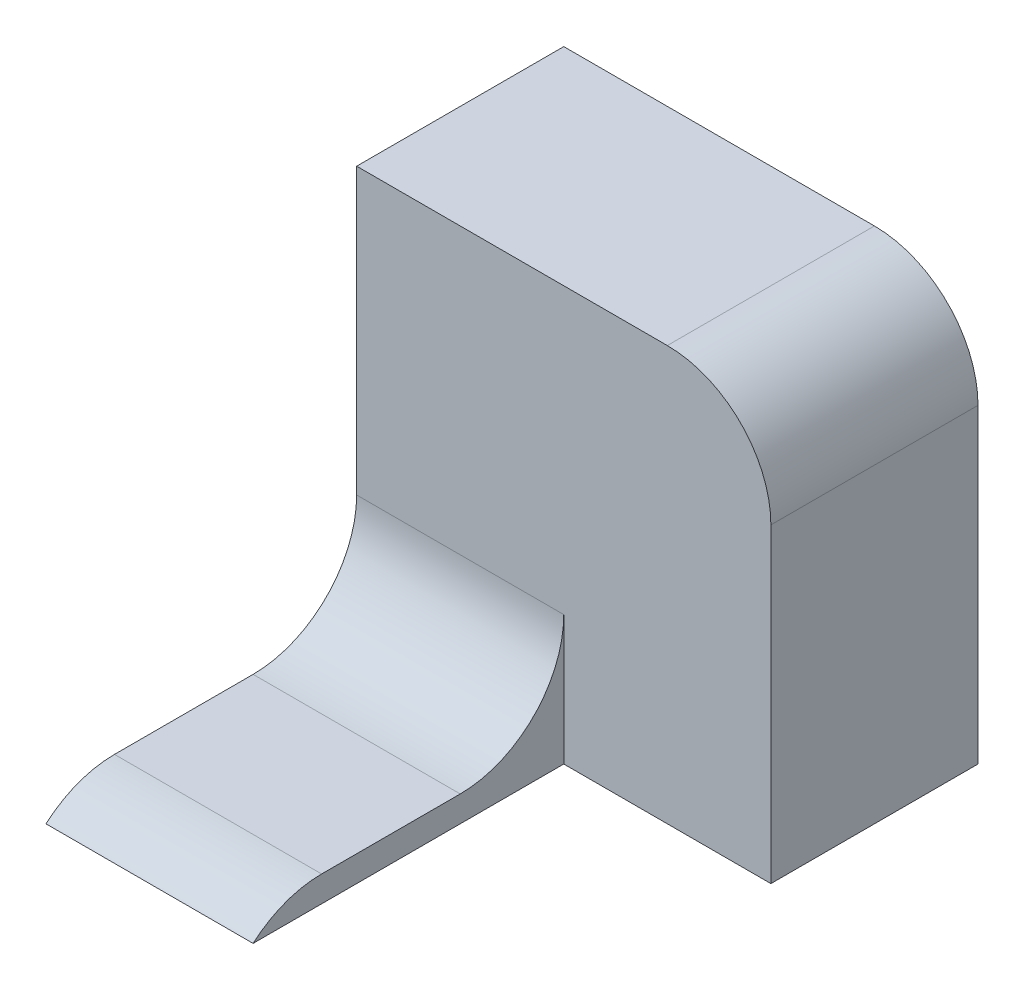
SolidWorks part; units mm, degrees
ref_plane "Front Plane" through (0, 0, 0) normal (0, 0, 1) x (1, 0, 0)
ref_plane "Top Plane" through (0, 0, 0) normal (0, 1, 0) x (1, 0, 0)
ref_plane "Right Plane" through (0, 0, 0) normal (1, 0, 0) x (0, 0, -1)
sketch "Sketch1" plane through (0, 0, 0) normal (0, 0, 1) x (1, 0, 0)
  line L1 (-30, -2.5) -> (-10, -2.5)
  line L2 (-10, -2.5) -> (-10, 0)
  line L3 (-10, 0) -> (-30, 0)
  line L4 (-30, 0) -> (-30, -2.5)
  dimension "D1" = 20
  dimension "Width" = 2.5
extrude "Boss-Extrude1" add sketch "Sketch1" along normal blind 30
sketch "Sketch2" plane through (0, 0, 0) normal (0, 0, 1) x (1, 0, 0)
  line L1 (-30, -2.5) -> (10, -2.5)
  line L2 (10, -2.5) -> (10, 37.5)
  line L3 (10, 37.5) -> (-30, 37.5)
  line L4 (-30, 37.5) -> (-30, -2.5)
  dimension "D1" = 40
  dimension "Width" = 40
extrude "Boss-Extrude2" add sketch "Sketch2" against normal blind 20
fillet "Fillet1" radius 10 3 edges at (-20, 0, 0) (10, 37.5, -10) (-20, 0, 30)
